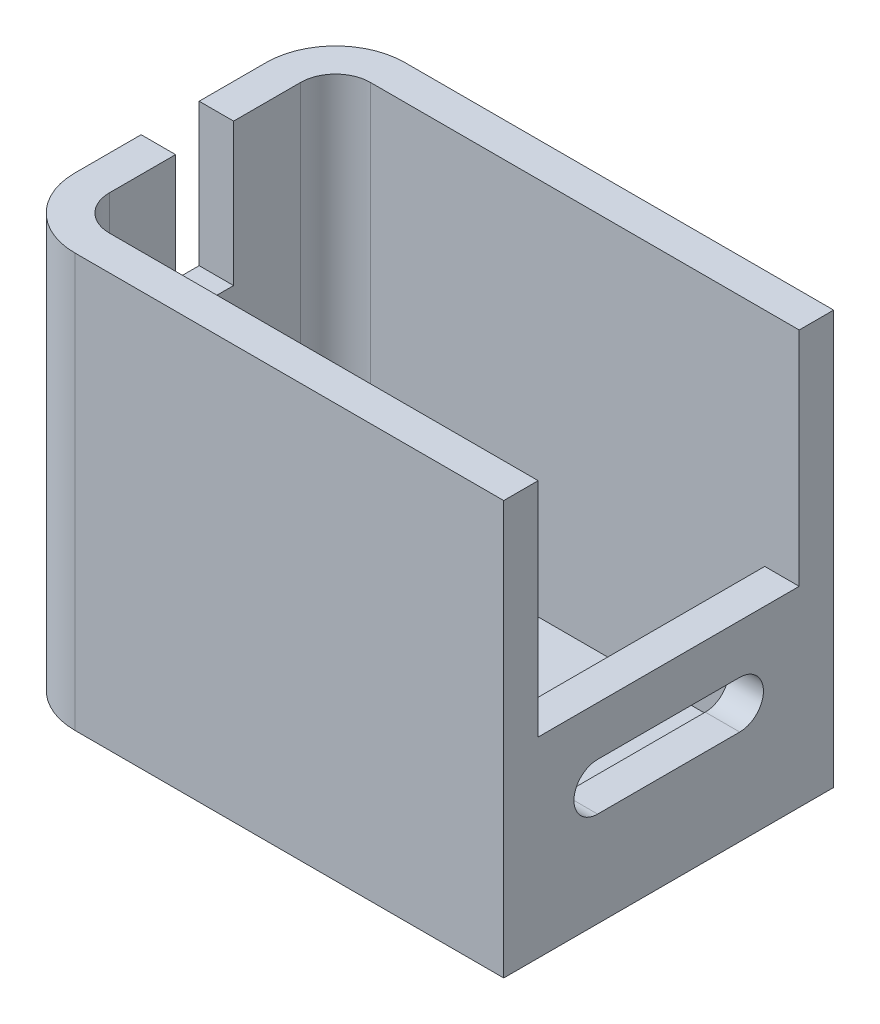
SolidWorks part; units mm, degrees
ref_plane "Front Plane" through (0, 0, 0) normal (0, 0, 1) x (1, 0, 0)
ref_plane "Top Plane" through (0, 0, 0) normal (0, 1, 0) x (1, 0, 0)
ref_plane "Right Plane" through (0, 0, 0) normal (1, 0, 0) x (0, 0, -1)
sketch "Sketch2" plane through (0, 0, 0) normal (0, 1, 0) x (1, 0, 0)
  line L0 (-21.2102, -2.5614) -> (-16.1598, -2.5614)
  line L1 (-21.2102, 2.4886) -> (-16.1598, 2.4886)
  line L2 (21.2102, 11.3625) -> (-13.1298, 11.3625)
  line L3 (21.2102, 11.3625) -> (21.2102, -11.3625)
  line L4 (21.2102, -11.3625) -> (-13.1298, -11.3625)
  line L5 (-16.1598, 8.3325) -> (-16.1598, -8.3325)
  line L6 (-21.2102, 2.4886) -> (-21.2102, -2.5614)
  arc A0 (-13.1298, -11.3625) -> (-16.1598, -8.3325) centre (-13.1298, -8.3325) cw
  arc A1 (-13.1298, 11.3625) -> (-16.1598, 8.3325) centre (-13.1298, 8.3325) ccw
extrude "Boss-Extrude1" add sketch "Sketch2" along normal blind 33 contours L2 A1 L5 A0 L4 L3 region at (2.6091, 0, 0)
shell "Shell2" thickness 3 removed face at (-2.9023, 33, 0) outward yes
sketch "Sketch5" plane through (21.2102, 0, 0) normal (-1, 0, 0) x (0, 0, 1)
  line L1 (11.3625, 0) -> (-11.3625, 0)
  line L2 (11.3625, 0) -> (11.3625, 33)
  line L3 (11.3625, 33) -> (-11.3625, 33)
  line L4 (-11.3625, 0) -> (-11.3625, 33)
extrude "Cut-Extrude1" cut sketch "Sketch5" against normal blind 33
extrude "Cut-Extrude3" cut sketch "Sketch2<4>" along normal blind 33 from offset 20.6 contours L1 L6 L0 L5 region at (-18.685, 0, 0.0364)
sketch "Sketch2<4>" plane through (0, 0, 0) normal (0, 1, 0) x (1, 0, 0) same geometry as "Sketch2"
extrude "Boss-Extrude2" add sketch "Sketch2<6>" against normal blind 4 contours L2 A1 L5 A0 L4 L3 region at (2.6091, 0, 0)
sketch "Sketch2<6>" plane through (0, 0, 0) normal (0, 1, 0) x (1, 0, 0) same geometry as "Sketch2"
sketch "Sketch6" plane through (0, 0, 0) normal (0, 1, 0) x (1, 0, 0)
  line L0 (24.2102, 11.3625) -> (24.2102, -11.3625)
  line L1 (24.2102, -11.3625) -> (21.2102, -11.3625)
  line L2 (24.2102, -11.3625) -> (-13.1298, -11.3625) construction
  line L3 (21.2102, -11.3625) -> (21.2102, 11.3625)
  line L4 (24.2102, 11.3625) -> (-13.1298, 11.3625) construction
  line L5 (21.2102, 11.3625) -> (24.2102, 11.3625)
  dimension "D1" = 3
extrude "Boss-Extrude3" add sketch "Sketch6" along normal blind 13.67
sketch "Sketch7" plane through (24.2102, 0, 0) normal (1, 0, 0) x (0, 0, -1)
  line L0 (-6.1859, 7.3336) -> (6.1859, 7.3336) construction
  line L1 (-6.1859, 9.3956) -> (6.1859, 9.3956)
  line L2 (-6.1859, 5.2716) -> (6.1859, 5.2716)
  arc A0 (-6.1859, 9.3956) -> (-6.1859, 5.2716) centre (-6.1859, 7.3336) ccw
  arc A1 (6.1859, 5.2716) -> (6.1859, 9.3956) centre (6.1859, 7.3336) ccw
  point P2 (0, 7.3336)
extrude "Cut-Extrude5" cut sketch "Sketch7" against normal blind 13.67
